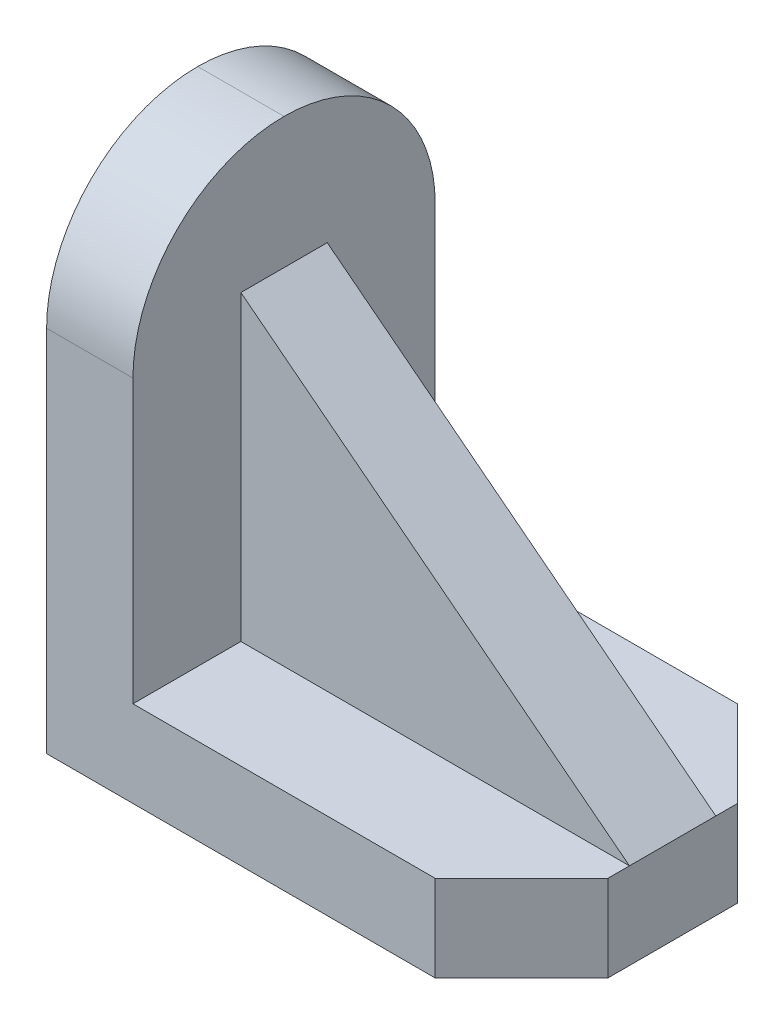
SolidWorks part; units mm, degrees
ref_plane "Front Plane" through (0, 0, 0) normal (0, 0, 1) x (1, 0, 0)
ref_plane "Top Plane" through (0, 0, 0) normal (0, 1, 0) x (1, 0, 0)
ref_plane "Right Plane" through (0, 0, 0) normal (1, 0, 0) x (0, 0, -1)
sketch "Sketch1" plane through (0, 0, 0) normal (0, 1, 0) x (1, 0, 0)
  line L0 (838.2, -228.6) -> (533.4, -533.4)
  line L1 (533.4, -533.4) -> (-838.2, -533.4)
  line L2 (838.2, -228.6) -> (838.2, 533.4)
  line L3 (838.2, 533.4) -> (-838.2, 533.4)
  line L4 (-838.2, -533.4) -> (-838.2, 533.4)
  line L5 (838.2, -533.4) -> (-838.2, 533.4) construction
  line L6 (838.2, 533.4) -> (-838.2, -533.4) construction
  point P0 (0, 0)
  point P8 (0, 0)
  dimension "D1" = 1676.4
  dimension "D2" = 1066.8
extrude "Boss-Extrude1" add sketch "Sketch1" along normal blind 304.8
chamfer "Chamfer1" distance 304.8 angle 45 1 edges at (838.2, 152.4, -533.4)
sketch "Sketch3" plane through (0, 304.8, 0) normal (0, 1, 0) x (1, 0, 0)
  line L0 (-838.2, -533.4) -> (533.4, -533.4) construction
  line L1 (-838.2, 533.4) -> (-533.4, 533.4)
  line L2 (-838.2, 533.4) -> (-838.2, -533.4)
  line L3 (-838.2, -533.4) -> (-533.4, -533.4)
  line L4 (-533.4, 533.4) -> (-533.4, -533.4)
  dimension "D1" = 304.8
extrude "Boss-Extrude2" add sketch "Sketch3" along normal blind 1529.08
fillet "Fillet1" radius 533.4 2 edges at (-685.8, 1833.88, -533.4) (-685.8, 1833.88, 533.4)
sketch "Sketch4" plane through (0, 0, 0) normal (0, 0, 1) x (1, 0, 0)
  line L6 (-533.4, 1371.6) -> (838.2, 304.8)
  line L7 (-533.4, 1300.48) -> (-533.4, 1833.88) construction
  line L8 (838.2, 304.8) -> (-533.4, 304.8)
  line L9 (-533.4, 304.8) -> (-533.4, 1371.6)
  dimension "D1" = 1066.8
extrude "Boss-Extrude3" add sketch "Sketch4" along normal mid plane 304.8 contours L6 L8 L9
